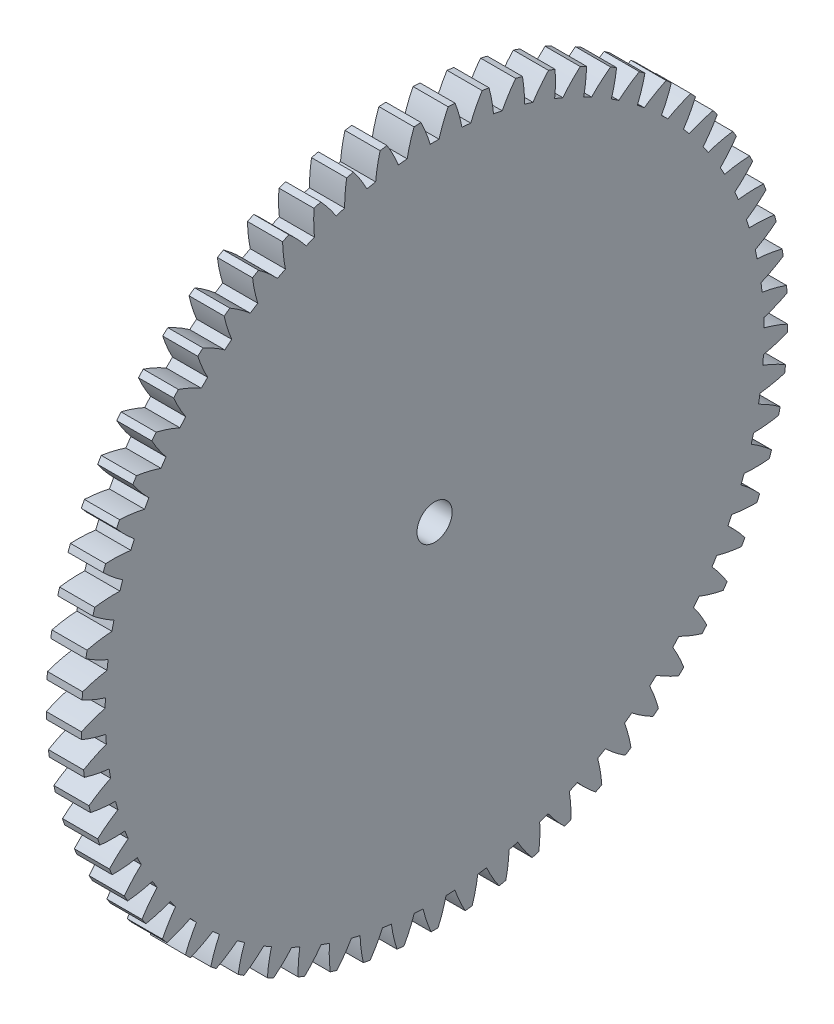
SolidWorks part; units mm, degrees
ref_plane "Plane1" through (0, 0, 0) normal (0, 0, 1) x (1, 0, 0)
ref_plane "Plane2" through (0, 0, 0) normal (0, 1, 0) x (1, 0, 0)
ref_plane "Plane3" through (0, 0, 0) normal (1, 0, 0) x (0, 0, -1)
sketch "HoldingSke" plane through (0, 0, 0) normal (0, 1, 0) x (1, 0, 0)
  line L0 (0, 0) -> (0.2817, -0.6042)
  line L1 (-15, 0) -> (100, 0) construction
  line L2 (0, 0) -> (-2.1039, 2.3779)
  line L3 (0, 0) -> (-11.863, 4.5341)
  line L4 (0, 0) -> (3.6497, 7.8269)
  line L5 (0, 0) -> (-46.8476, -17.4728)
  line L6 (0, 0) -> (-4.1448, -2.7965)
  line L7 (-2.1039, 2.3779) -> (8.6586, 51.2059)
  line L8 (-76.2, 54.61) -> (-75.3, 54.61)
  line L9 (-71.009, 38.7566) -> (-53.1078, 45.2721)
  line L10 (-76.2, 71.12) -> (104.1128, 71.12)
  line L11 (0, 0) -> (-5, 0)
  line L12 (-76.2, 101.6) -> (-76.147, 101.6)
  line L13 (24.9733, 27.94) -> (52.9518, 28.4284)
  line L14 (24.9733, 27.94) -> (24.9743, 27.94)
  line L15 (24.9733, 27.94) -> (100.4006, 29.5858)
  line L16 (-63.627, -1.5) -> (-12.827, -1.5)
  circle A0 centre (0, 0) radius 2.5
  circle A1 centre (0, 0) radius 37.5
  circle A2 centre (0, 0) radius 37.5
  circle A3 centre (0, 0) radius 2.5
  dimension "Pitch_radius" = 180.3128
sketch "BasProSke" plane through (0, 0, 0) normal (0, 1, 0) x (1, 0, 0)
  line L0 (-10, 0) -> (60, 0) construction
  line L1 (0, 0) -> (0, 50.25)
  line L2 (0, 0) -> (5, 0)
  line L3 (5, 0) -> (5, 50.25)
  line L4 (5, 50.25) -> (0, 50.25)
revolve "Base-Revolve" add sketch "BasProSke" angle 360 about L0
sketch "TooCutSke" plane through (0, 0, 0) normal (1, 0, 0) x (0, 0, -1)
  line L1 (0, 0) -> (0, 107) construction
  line L2 (0, 0) -> (-1.2707, 48.7334) construction
  line L3 (0, 0) -> (-4.7094, 97.362) construction
  line L4 (-1.2707, 48.7334) -> (-2.3547, 48.681) construction
  arc A0 (0.6342, 46.8697) -> (-0.6342, 46.8697) centre (0, 0) ccw
  arc A1 (1.9459, 50.2377) -> (-1.9459, 50.2377) centre (0, 0) ccw
  circle A2 centre (0, 0) radius 48.75 construction
  circle A3 centre (0, 0) radius 45.81 construction
  arc A4 (-0.6342, 46.8697) -> (-1.9459, 50.2377) centre (-19.3825, 41.5075) ccw
  arc A5 (1.9459, 50.2377) -> (0.6342, 46.8697) centre (19.3825, 41.5075) ccw
extrude "ToothCut" cut sketch "TooCutSke" along normal through all
fillet "Breaks" [suppressed] radius 0.03 tangent propagation no
fillet "RootFillets" [suppressed] radius 0.376
pattern_circular "TeethCuts" count 65 every 5.538 about axis through (-10, 0, 0) along (1, 0, 0) of "ToothCut", "RootFillets", "Breaks"
sketch "HubNeaOneSke" plane through (0, 0, 0) normal (-1, 0, 0) x (0, 0, 1)
  circle A0 centre (0, 0) radius 37.5
  dimension "Diameter" = 75
extrude "HubNearOne" [suppressed] add sketch "HubNeaOneSke" along normal blind 45.0001
sketch "HubNeaBotSke" plane through (0, 0, 0) normal (-1, 0, 0) x (0, 0, 1)
  circle A0 centre (0, 0) radius 37.5
  dimension "Diameter" = 75
extrude "HubNearBoth" [suppressed] add sketch "HubNeaBotSke" along normal blind 22.5
ref_plane "FarPln" through (5, 0, 0) normal (1, 0, 0) x (0, 0, -1)
sketch "HubFarSke" plane through (5, 0, 0) normal (1, 0, 0) x (0, 0, -1)
  circle A0 centre (0, 0) radius 37.5
  dimension "Diameter" = 75
extrude "HubFar" [suppressed] add sketch "HubFarSke" along normal blind 22.5
sketch "BorSke" plane through (0, 0, 0) normal (1, 0, 0) x (0, 0, -1)
  circle A0 centre (0, 0) radius 2.5
  dimension "Diameter" = 5
extrude "Bore" cut sketch "BorSke" along normal mid plane 100.0001
sketch "KeySke" plane through (0, 0, 0) normal (1, 0, 0) x (0, 0, -1)
  line L0 (-1, 0) -> (-1, 3.4)
  line L1 (-1, 3.4) -> (1, 3.4)
  line L2 (1, 3.4) -> (1, 0)
  line L3 (0, 0) -> (0, 34) construction
  line L4 (-1, 0) -> (1, 0)
  dimension "Width" = 2
extrude "Keyway" [suppressed] cut sketch "KeySke" along normal mid plane 100.0001
pattern_circular "Keyway2" [suppressed] count 2 every 90 about axis through (-10, 0, 0) along (1, 0, 0) reverse direction yes
equation "' \"Module@HoldingSke\" = 6.35"
equation "' \"Num_teeth@HoldingSke\" = 12"
equation "' \"Ap@HoldingSke\" =  20"
equation "' \"Ap@HoldingSke\" = 20"
equation "' \"Width@HoldingSke\" = 0.5 * 25.4"
equation "' \"Hub_dia@HoldingSke\"= 1 * 25.4"
equation "' \"Hub_dia@HoldingSke\" = 1 * 25.4"
equation "' \"Overall_len@HoldingSke\" = 1.0 * 25.4"
equation "' \"Bore@HoldingSke\" = 0.75 * 25.4"
equation "' \"T_dim@HoldingSke\" = 0.1 * 25.4"
equation "' \"Width@KeySke\" = 0.25 * 25.4"
equation "' \"Show_teeth@HoldingSke\" = 13"
equation "' \"Backlash@HoldingSke\" = 0.009 * 25.4"
equation "' \"Addendum_fac@HoldingSke\" = 1.0"
equation "' \"Dedendum_fac@HoldingSke\" = 1.25"
equation "' \"Dedendum_add@HoldingSke\" = 0.00005 * 25.4"
equation "' \"Clearance_fac@HoldingSke\" = 0.25"
equation "\"Pitch@HoldingSke\" = 1 / \"Module@HoldingSke\""
equation "\"Overcut_dia@TooCutSke\" = (\"Num_teeth@HoldingSke\" + 2 * \"Addendum_fac@HoldingSke\") / \"Pitch@HoldingSke\" + 0.002 * 25.4"
equation "\"Pitch_dia@TooCutSke\" = \"Num_teeth@HoldingSke\" / \"Pitch@HoldingSke\""
equation "\"Base_dia@TooCutSke\" = \"Num_teeth@HoldingSke\" / \"Pitch@HoldingSke\" * cos((\"Ap@HoldingSke\"  * 3.14159265 / 180))"
equation "\"Root_dia@TooCutSke\" = (\"Num_teeth@HoldingSke\" + 2) / \"Pitch@HoldingSke\" - 2 * (\"Addendum_fac@HoldingSke\" + \"Dedendum_fac@HoldingSke\") / \"Pitch@HoldingSke\" - \"Dedendum_add@HoldingSke\" * 2"
equation "\"Half_ang@TooCutSke\" = 180 / \"Num_teeth@HoldingSke\""
equation "\"Half_CT@TooCutSke\" = \"Num_teeth@HoldingSke\" / \"Pitch@HoldingSke\" * sin((3.14159265 / 2 / \"Num_teeth@HoldingSke\")) / 2 - 7 * \"Backlash@HoldingSke\" / 4"
equation "\"Flank_rad@TooCutSke\" = \"Num_teeth@HoldingSke\" / \"Pitch@HoldingSke\" / 5"
equation "\"Radius@RootFillets\" = \"Clearance_fac@HoldingSke\" / \"Pitch@HoldingSke\" + \"Dedendum_add@HoldingSke\""
equation "\"Break_rad@Breaks\" = 0.02 / \"Pitch@HoldingSke\""
equation "\"Thickness@HoldingSke\" = \"Width@HoldingSke\""
equation "\"OAL@HoldingSke\" = \"Thickness@HoldingSke\""
equation "\"MHD@HoldingSke\" = (\"Num_teeth@HoldingSke\" + 2) / \"Pitch@HoldingSke\" - 2 * (\"Addendum_fac@HoldingSke\" + \"Dedendum_fac@HoldingSke\")  / \"Pitch@HoldingSke\" - \"Dedendum_add@HoldingSke\" * 2"
equation "\"MBD@HoldingSke\" = (\"Num_teeth@HoldingSke\" + 2) / \"Pitch@HoldingSke\" - 2 * (\"Addendum_fac@HoldingSke\" + \"Dedendum_fac@HoldingSke\")  / \"Pitch@HoldingSke\" - \"Dedendum_add@HoldingSke\" * 2 - 0.002 * 25.4"
equation "\"MHD@HoldingSke\" = ((sgn( \"MHD@HoldingSke\" - \"Hub_dia@HoldingSke\" )-1)*( \"MHD@HoldingSke\" - \"Hub_dia@HoldingSke\" ))/-2+ \"Hub_dia@HoldingSke\""
equation "\"MBD@HoldingSke\" = ((sgn( \"MBD@HoldingSke\" - \"Bore@HoldingSke\" )-1)*( \"MBD@HoldingSke\" - \"Bore@HoldingSke\" ))/-2+ \"Bore@HoldingSke\""
equation "\"OAL@HoldingSke\" = ((sgn( \"OAL@HoldingSke\" - \"Overall_len@HoldingSke\" )+1)*( \"OAL@HoldingSke\" - \"Overall_len@HoldingSke\" ))/2 + \"Overall_len@HoldingSke\" + 0.000002 * 25.4"
equation "\"Num_teeth@TeethCuts\" = int( \"Show_teeth@HoldingSke\" ) + 1"
equation "\"Num_teeth@TeethCuts\" = ((sgn( \"Num_teeth@TeethCuts\" - \"Num_teeth@HoldingSke\" )-1)*( \"Num_teeth@TeethCuts\" - \"Num_teeth@HoldingSke\" ))/-2+ \"Num_teeth@HoldingSke\""
equation "\"Num_teeth@TeethCuts\" = ((sgn( \"Num_teeth@TeethCuts\" - 2.0)+1)*( \"Num_teeth@TeethCuts\" - 2.0))/2 +2.0"
equation "\"Angle@TeethCuts\" = 360.0 / \"Num_teeth@HoldingSke\""
equation "\"Diameter@BasProSke\" = (\"Num_teeth@HoldingSke\" + 2 * \"Addendum_fac@HoldingSke\") / \"Pitch@HoldingSke\""
equation "\"Thickness@BasProSke\"  = \"Thickness@HoldingSke\""
equation "' \"Fillet_rad@BasProSke\" =  \"Thickness@HoldingSke\" * 0.05"
equation "' \"Fillet_rad@BasProSke\" = \"Thickness@HoldingSke\" * 0.05"
equation "\"MHD@HoldingSke\" = ((sgn( \"MHD@HoldingSke\" - \"Root_dia@TooCutSke\" )-1)*( \"MHD@HoldingSke\" - \"Root_dia@TooCutSke\" ))/-2+ \"Root_dia@TooCutSke\""
equation "\"Diameter@HubNeaOneSke\" = \"MHD@HoldingSke\""
equation "\"Length@HubNearOne\" = \"OAL@HoldingSke\" - \"Thickness@BasProSke\""
equation "\"Diameter@HubNeaBotSke\" = \"MHD@HoldingSke\""
equation "\"Length@HubNearBoth\" = ( \"OAL@HoldingSke\" - \"Thickness@BasProSke\" ) / 2.0"
equation "\"Thickness@FarPln\" = \"Thickness@BasProSke\""
equation "\"Diameter@HubFarSke\" = \"MHD@HoldingSke\""
equation "\"Length@HubFar\" = ( \"OAL@HoldingSke\" - \"Thickness@BasProSke\" ) / 2.0"
equation "\"Diameter@BorSke\" = \"MBD@HoldingSke\""
equation "\"D1@Bore\" = \"OAL@HoldingSke\" * 2.0"
equation "\"D1@Keyway\" = \"OAL@HoldingSke\" * 2.0"
equation "\"Offset@KeySke\" = \"T_dim@HoldingSke\" + \"MBD@HoldingSke\" / 2.0"
